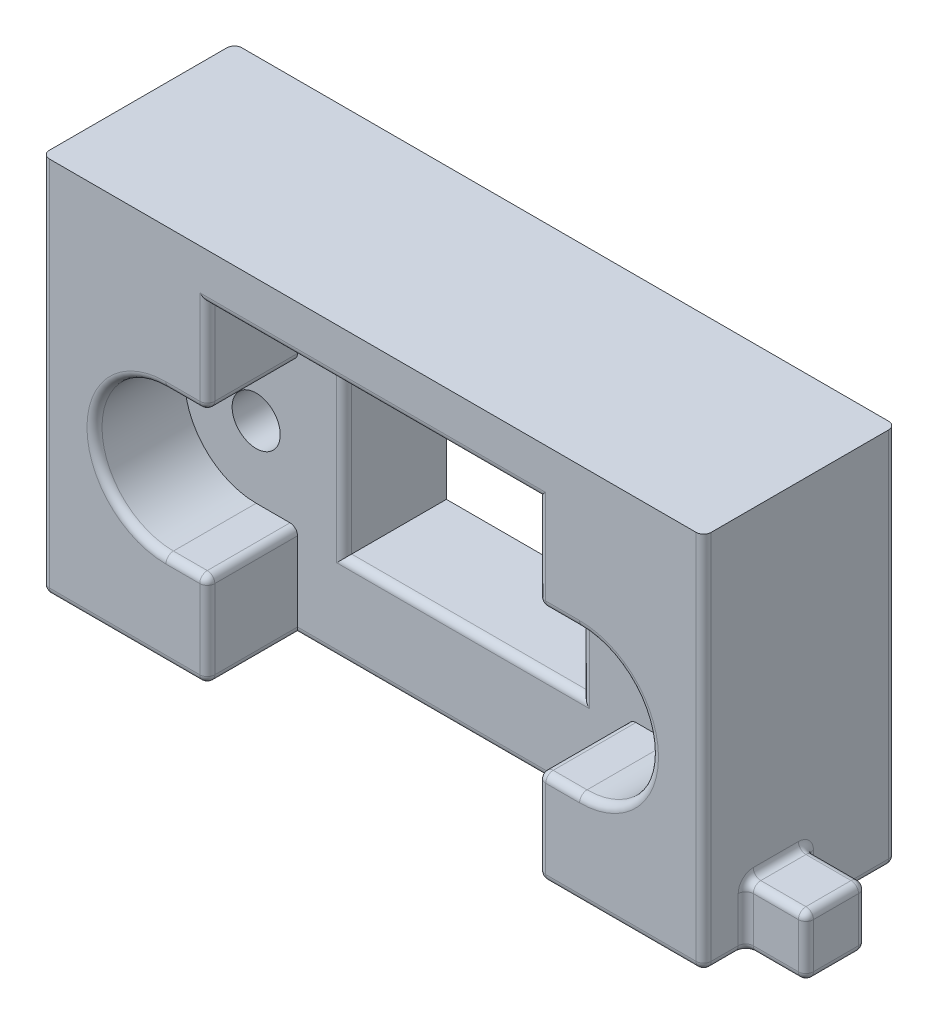
SolidWorks part; units mm, degrees
ref_plane "Front Plane" through (0, 0, 0) normal (0, 0, 1) x (1, 0, 0)
ref_plane "Top Plane" through (0, 0, 0) normal (0, 1, 0) x (1, 0, 0)
ref_plane "Right Plane" through (0, 0, 0) normal (1, 0, 0) x (0, 0, -1)
sketch "Sketch1" plane through (0, 0, 0) normal (0, 0, 1) x (1, 0, 0)
  line L0 (13.75, 0) -> (-13.75, 0) construction
  line L1 (-11, 11) -> (11, 11)
  line L2 (-11, 11) -> (-11, 4.75)
  line L3 (-11, -11) -> (11, -11)
  line L4 (11, 11) -> (11, 4.75)
  line L5 (0, -11) -> (0, 11) construction
  line L6 (-11, 0) -> (11, 0) construction
  line L7 (-13.75, 4.75) -> (-11, 4.75)
  line L8 (-13.75, -4.75) -> (-11, -4.75)
  line L9 (13.75, 4.75) -> (11, 4.75)
  line L10 (13.75, -4.75) -> (11, -4.75)
  line L11 (-11, -4.75) -> (-11, -11)
  line L12 (11, -4.75) -> (11, -11)
  line L13 (0, 11) -> (0, 14.2) construction
  line L14 (-7.9, 8.25) -> (7.9, 8.25)
  line L15 (-7.9, 8.25) -> (-7.9, -5)
  line L16 (-7.9, -5) -> (7.9, -5)
  line L17 (7.9, 8.25) -> (7.9, -5)
  line L18 (0, -5) -> (0, 8.25) construction
  line L19 (-7.9, 1.625) -> (7.9, 1.625) construction
  line L20 (-22, 14.2) -> (22, 14.2)
  line L21 (22, 14.2) -> (22, -11)
  line L22 (22, -11) -> (-22, -11)
  line L23 (-22, -11) -> (-22, 14.2)
  circle A0 centre (-13.75, 0) radius 1.6
  circle A1 centre (13.75, 0) radius 1.6
  arc A2 (-13.75, 4.75) -> (-13.75, -4.75) centre (-13.75, 0) ccw
  arc A3 (13.75, -4.75) -> (13.75, 4.75) centre (13.75, 0) ccw
  point P0 (0, 0)
  point P7 (0, 0)
  point P9 (0, 1.625)
  point P25 (0, 14.2)
  dimension "D4" = 3.2
  dimension "D5" = 3.2
  dimension "D6" = 9.5
  dimension "D7" = 9.5
  dimension "D1" = 22
  dimension "D2" = 22
  dimension "D3" = 27.5
  dimension "D8" = 15.8
  dimension "D9" = 13.25
  dimension "D10" = 6
  dimension "D11" = 3.2
  dimension "D12" = 44
extrude "Boss-Extrude1" add sketch "Sketch1" against normal blind 6.8 contours A3 L10 L12 L22 L21 L20 L23 L11 L8 A2 L7 L2 L1 L4 L9 | L10 A3 L9 L4 L1 L2 L7 A2 L8 L11 L3 L12 A1 A0 L14 L17 L16 L15 region at (-11.5071, 7.875, 0) region at (0, 10.5695, 0)
extrude "Boss-Extrude4" add sketch "Sketch1<3>" along normal blind 6 contours A3 L10 L12 L22 L21 L20 L23 L11 L8 A2 L7 L2 L1 L4 L9 region at (-11.5071, 7.875, 0)
sketch "Sketch1<3>" plane through (0, 0, 0) normal (0, 0, 1) x (1, 0, 0) same geometry as "Sketch1"
sketch "Sketch6" plane through (22, 0, 0) normal (1, 0, 0) x (0, 0, -1)
  line L0 (6.8, -11) -> (-6, -11) construction
  line L1 (-3.2, -11) -> (0.8, -11)
  line L2 (-3.2, -11) -> (-3.2, -7)
  line L3 (-3.2, -7) -> (0.8, -7)
  line L4 (0.8, -11) -> (0.8, -7)
  line L5 (6.8, 14.2) -> (6.8, -11) construction
  dimension "D1" = 4
  dimension "D2" = 4
  dimension "D3" = 6
extrude "Boss-Extrude6" add sketch "Sketch6" along normal blind 4
fillet "Fillet1" radius 0.5 43 edges at (22, -7, 1.2) (24, -11, 3.2) (24, -11, -0.8) (26, -9, -0.8) (24, -7, -0.8) (22, -9, -0.8) (24, -7, 3.2) (22, -9, 3.2) (26, -9, 3.2) (26, -7, 1.2) (26, -11, 1.2) (22, 1.6, 6) (22, -11, 4.6) (22, -11, -3.8) (-22, 1.6, 6) (-22, -11, -0.4) (0, -11, -6.8) (22, 1.6, -6.8) (-22, 1.6, -6.8) (-12.375, 4.75, 6) (-18.5, 0, 6) (12.375, -4.75, 6) (18.5, 0, 6) (-7.9, 1.625, 0) (0, -5, 0) (7.9, 1.625, 0) (0, 8.25, 0) (-16.5, -11, 6) (16.5, -11, 6) (-11, 7.875, 6) (-12.375, -4.75, 6) (-11, -7.875, 6) (11, -7.875, 6) (12.375, 4.75, 6) (11, 7.875, 6) (0, 11, 6) (11, -4.75, 3) (-11, -4.75, 3) (-11, 4.75, 3) (11, 4.75, 3) (-11, -11, 3) (0, -11, 0) (11, -11, 3)
